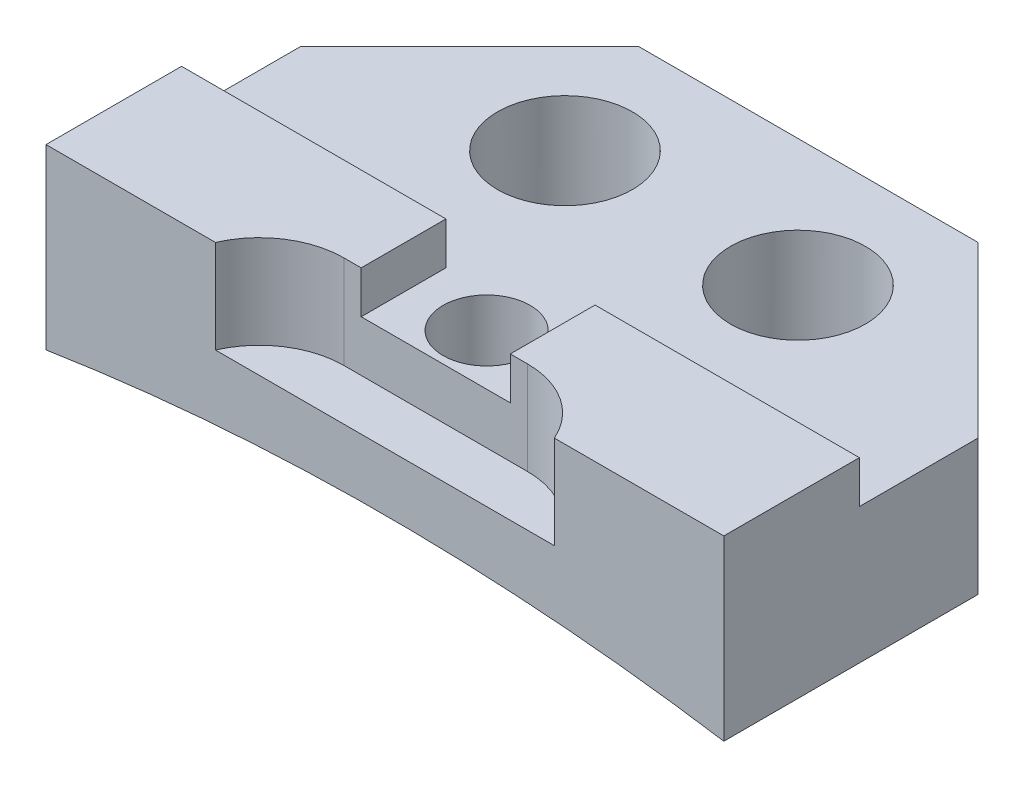
SolidWorks part; units mm, degrees
ref_plane "Front Plane" through (0, 0, 0) normal (0, 0, 1) x (1, 0, 0)
ref_plane "Top Plane" through (0, 0, 0) normal (0, 1, 0) x (1, 0, 0)
ref_plane "Right Plane" through (0, 0, 0) normal (1, 0, 0) x (0, 0, -1)
sketch "Sketch1" plane through (0, 0, 0) normal (0, 1, 0) x (1, 0, 0)
  line L0 (-28.5118, -10.9672) -> (-22.1618, -4.6172)
  line L1 (-22.1618, -4.6172) -> (-9.4618, -4.6172)
  line L2 (-28.5118, -10.9672) -> (-28.5118, -12.5547)
  line L3 (-28.5118, -12.5547) -> (-3.1118, -12.5547)
  line L4 (-3.1118, -10.9672) -> (-3.1118, -12.5547)
  line L5 (-9.4618, -4.6172) -> (-3.1118, -10.9672)
  line L6 (-15.8118, -12.5547) -> (-15.8118, -4.6172) construction
  line L8 (-3.1118, -10.9672) -> (-3.1118, -4.6172) construction
  line L9 (-3.1118, -4.6172) -> (-9.4618, -4.6172) construction
  dimension "D1" = 12.7
  dimension "D2" = 7.9375
  dimension "D3" = 25.4
extrude "Boss-Extrude1" add sketch "Sketch1" along normal blind 3.175
sketch "Sketch2" plane through (0, 0, 12.5547) normal (0, 0, 1) x (1, 0, 0)
  circle A0 centre (-15.8118, -82.8523) radius 83.82
  dimension "D1" = 167.64
extrude "Cut-Extrude1" cut sketch "Sketch2" against normal through all both and the other way through all
sketch "Sketch5" plane through (0, 0, 4.6172) normal (0, 0, -1) x (-1, 0, 0)
  line L0 (3.1118, 3.175) -> (3.1118, 0) construction
  line L1 (3.1118, 3.175) -> (3.1118, 0)
  line L4 (28.5118, 3.175) -> (28.5118, 0) construction
  line L5 (28.5118, 3.175) -> (28.5118, 0)
  line L6 (28.5118, -1.9021) -> (28.5118, 0)
  line L7 (3.1118, -1.9021) -> (3.1118, 0)
  line L8 (3.1118, 3.175) -> (28.5118, 3.175)
  arc A0 (3.1118, -1.9021) -> (28.5118, -1.9021) centre (15.8118, -82.8523) cw
  arc A1 (28.5118, 0) -> (3.1118, 0) centre (15.8118, -82.8523) ccw construction
  arc A2 (28.5118, 0) -> (3.1118, 0) centre (15.8118, -82.8523) ccw construction
  dimension "D1" = 81.9404
extrude "Boss-Extrude2" add sketch "Sketch5" against normal blind 15.875
chamfer "Chamfer1" distance 6.35 angle 45 2 edges at (-28.5118, 0.6365, 4.6172) (-3.1118, 0.6365, 4.6172)
hole_wizard "#8 (0.199) Diameter Hole1" positions "Sketch3" profile "Sketch4" hole size "#8" standard "ANSI Inch" end condition through all
sketch "Sketch3" plane through (0, 3.175, 0) normal (0, 1, 0) x (1, 0, 0)
  line L0 (-15.8118, -4.6172) -> (-15.8118, 3.4006) construction
  line L1 (-9.4618, -4.6172) -> (-22.1618, -4.6172) construction
  point P0 (-20.1775, -9.3797)
  point P12 (-11.4462, -9.3797)
  dimension "D1" = 4.7625
  dimension "D2" = 4.3656
sketch "Sketch4" plane through (-20.1775, 3.175, 9.3797) normal (1, 0, 0) x (0, 0, 1)
  line L0 (0, 0) -> (0, 5.0771)
  line L1 (0, 5.0771) -> (2.5273, 5.0771)
  line L2 (2.5273, 5.0771) -> (2.5273, 0)
  line L5 (2.5273, 0) -> (0, 0)
  line L11 (0, -6.35) -> (0, 107.95) construction
  dimension "Thru Hole Dia." = 5.0546
  dimension "Thru Hole Depth" = 5.0771
chamfer "Chamfer2" [suppressed] distance 1.905 angle 45
sketch "Sketch8" plane through (0, 3.175, 0) normal (0, 1, 0) x (1, 0, 0)
  line L1 (-22.1618, -20.4922) -> (-9.4618, -20.4922)
  line L3 (-19.2519, -18.5872) -> (-12.3718, -18.5872)
  line L5 (-28.5118, -20.4922) -> (-3.1118, -20.4922) construction
  line L6 (-15.8118, -20.4922) -> (-15.8118, -12.2234) construction
  arc A0 (-22.1618, -20.4922) -> (-19.2519, -18.5872) centre (-19.2519, -21.7622) cw
  arc A1 (-9.4618, -20.4922) -> (-12.3718, -18.5872) centre (-12.3718, -21.7622) ccw
  point P13 (-15.8118, -20.4922)
  point P14 (-15.8118, -20.4922)
  dimension "D3" = 3.175
  dimension "D1" = 1.905
  dimension "D2" = 12.7
extrude "Cut-Extrude3" cut sketch "Sketch8" against normal blind 1.905
sketch "Sketch6" plane through (0, 3.175, 0) normal (0, 1, 0) x (1, 0, 0)
  circle A0 centre (-15.81, -16.6822) radius 1.6319 construction
  circle A1 centre (-15.81, -16.6822) radius 1.6319
extrude "Cut-Extrude2" cut sketch "Sketch6" against normal through all
sketch "Sketch7" plane through (0, 3.175, 0) normal (0, 1, 0) x (1, 0, 0)
  line L0 (-15.8118, -2.4451) -> (-15.8118, -24.8094) construction
  line L1 (-9.4618, -4.6172) -> (-22.1618, -4.6172) construction
  line L2 (-28.5118, -10.9672) -> (-28.5118, -20.4922) construction
  line L3 (-28.5118, -15.4122) -> (-18.6058, -15.4122)
  line L4 (-28.5118, -15.4122) -> (-28.5118, -20.4922)
  line L5 (-19.2519, -18.5872) -> (-18.6058, -18.5872)
  line L6 (-18.6058, -15.4122) -> (-18.6058, -18.5872)
  line L8 (-13.0178, -15.4122) -> (-13.0178, -18.5872)
  line L9 (-12.3718, -18.5872) -> (-13.0178, -18.5872)
  line L10 (-3.1118, -15.4122) -> (-3.1118, -20.4922)
  line L11 (-3.1118, -15.4122) -> (-13.0178, -15.4122)
  line L12 (-19.2519, -18.5872) -> (-12.3718, -18.5872) construction
  line L14 (-9.4618, -20.4922) -> (-3.1118, -20.4922) construction
  line L16 (-9.4618, -20.4922) -> (-3.1118, -20.4922)
  line L17 (-28.5118, -20.4922) -> (-22.1618, -20.4922) construction
  line L18 (-28.5118, -20.4922) -> (-22.1618, -20.4922)
  arc A0 (-9.4618, -20.4922) -> (-12.3718, -18.5872) centre (-12.3718, -21.7622) ccw construction
  arc A1 (-9.4618, -20.4922) -> (-12.3718, -18.5872) centre (-12.3718, -21.7622) ccw
  arc A2 (-19.2519, -18.5872) -> (-22.1618, -20.4922) centre (-19.2519, -21.7622) ccw construction
  arc A3 (-19.2519, -18.5872) -> (-22.1618, -20.4922) centre (-19.2519, -21.7622) ccw
  point P6 (-15.8118, -4.6172)
  dimension "D1" = 2.794
  dimension "D2" = 3.175
extrude "Boss-Extrude3" add sketch "Sketch7" along normal blind 1.5875
